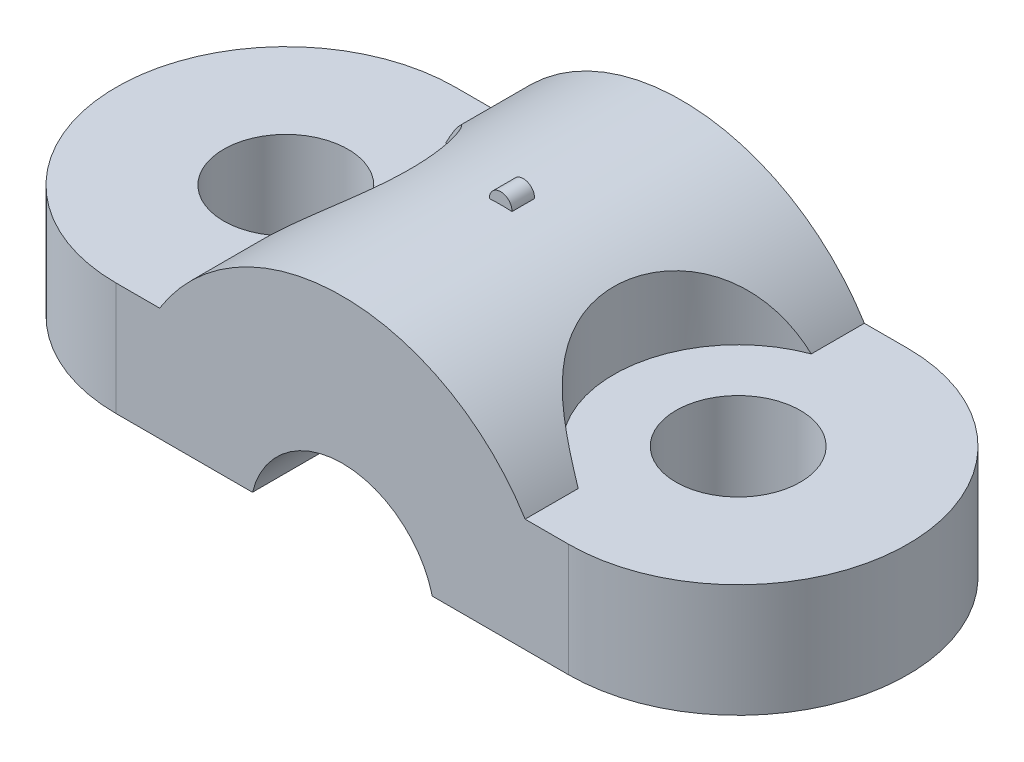
SolidWorks part; units mm, degrees
ref_plane "Front Plane" through (0, 0, 0) normal (0, 0, 1) x (1, 0, 0)
ref_plane "Top Plane" through (0, 0, 0) normal (0, 1, 0) x (1, 0, 0)
ref_plane "Right Plane" through (0, 0, 0) normal (1, 0, 0) x (0, 0, -1)
sketch "Sketch1" plane through (0, 0, 0) normal (0, 1, 0) x (1, 0, 0)
  line L0 (-10, 7.5) -> (10, 7.5)
  line L1 (-10, -7.5) -> (10, -7.5)
  line L2 (-8.08, 7.5) -> (-8.08, 5.154)
  line L3 (-8.08, -5.154) -> (-8.08, -7.5)
  line L4 (8.08, -7.5) -> (8.08, -5.154)
  line L5 (8.08, 7.5) -> (8.08, 5.154)
  circle A0 centre (-10, 0) radius 2.75
  circle A1 centre (10, 0) radius 2.75
  circle A2 centre (-10, 0) radius 5.5
  circle A3 centre (10, 0) radius 5.5
  circle A4 centre (-10, 0) radius 7.5
  circle A5 centre (10, 0) radius 7.5
  point P21 (0, 7.5)
  dimension "D1" = 5.5
  dimension "D2" = 2.75
  dimension "D3" = 4.75
  dimension "D4" = 20
  dimension "D5" = 10
  dimension "D6" = 8.08
  dimension "D7" = 8.08
extrude "Boss-Extrude1" add sketch "Sketch1" along normal blind 9.5 contours A5 L5 L0 L2 A4 L3 L1 L4 | L3 A4 L2 A2 | L5 A5 L4 A3 region at (0, 0, 0) region at (-4.1796, 0, -4.4796) region at (7.9246, 0, -6.202)
extrude "Boss-Extrude2" add sketch "Sketch1<3>" along normal blind 5 contours A2 A0 | A4 L3 A2 L2 | A3 A1 | A5 L5 A3 L4 | A4 L2 L0 | A4 L1 L3 | A5 L4 L1 | A5 L0 L5 region at (-9.0548, 0, -7.2616) region at (-8.5584, 0, -7.4252) region at (-8.5584, 0, 7.4252) region at (8.5584, 0, -7.4252) region at (-5.6106, 0, -3.0489) region at (15.1781, 0, -5.1781) region at (8.5584, 0, 7.4252) region at (13.0489, 0, -4.3894)
sketch "Sketch1<3>" plane through (0, 0, 0) normal (0, 1, 0) x (1, 0, 0) same geometry as "Sketch1"
sketch "Sketch3" plane through (0, 0, 7.5) normal (0, 0, 1) x (1, 0, 0)
  line L0 (-10, 0) -> (10, 0) construction
  line L3 (-8.08, 9.5) -> (-8.08, 5) construction
  line L4 (-8.08, 9.5) -> (8.08, 9.5) construction
  line L5 (8.08, 9.5) -> (8.08, 5) construction
  line L6 (-8.08, 9.5) -> (-8.08, 5)
  line L7 (-8.08, 9.5) -> (8.08, 9.5)
  line L8 (8.08, 9.5) -> (8.08, 5)
  circle A0 centre (0, -1) radius 4.1
  arc A1 (-8.08, 5) -> (8.08, 5) centre (0, -0.004) cw
  point P6 (0, 0)
  line M1 (-10, 0) -> (10, 0)
  line M4 (8.08, 9.5) -> (-8.08, 9.5)
  line M10 (8.08, 5) -> (8.08, 9.5)
  line M11 (-8.08, 9.5) -> (-8.08, 5)
  dimension "D2" = 8.2
  dimension "D1" = 1
extrude "Cut-Extrude2" cut sketch "Sketch3" against normal through all contours A1 L7 M11 | A1 M4 M10 | A0 M1 region at (-6.1679, 8.2305, 7.5) region at (6.1679, 8.2305, 7.5) region at (0, 1.2917, 7.5)
sketch "Sketch5" plane through (0, 5, 0) normal (0, 1, 0) x (1, 0, 0)
  line L0 (-17.5, 0) -> (17.5, 0) construction
  arc A0 (-10, 7.5) -> (-10, -7.5) centre (-10, 0) ccw construction
  arc A1 (10, -7.5) -> (10, 7.5) centre (10, 0) ccw construction
sketch "Sketch6" plane through (0, 0, 0) normal (0, -1, 0) x (1, 0, 0)
  line L0 (-17.5, 0) -> (17.5, 0) construction
  arc A0 (-10, 7.5) -> (-10, -7.5) centre (-10, 0) ccw construction
  arc A1 (10, -7.5) -> (10, 7.5) centre (10, 0) ccw construction
sketch3d "3DSketch1"
  line L0 (-17.5, 0, 0) -> (17.5, 0, 0) construction
  line L1 (-17.5, 5, 0) -> (17.5, 5, 0) construction
sketch "Sketch7" plane through (0, 0, 0) normal (0, 0, 1) x (1, 0, 0)
  line L0 (0, 0) -> (0, 15.6574) construction
  arc A0 (8.08, 5) -> (-8.08, 5) centre (0, -0.004) ccw construction
  arc A1 (8.08, 5) -> (-8.08, 5) centre (0, -0.004) ccw
  circle A2 centre (0, 9.5) radius 0.5
  dimension "D1" = 1
extrude "Boss-Extrude3" add sketch "Sketch7" along normal mid plane 1 contours A1 L0 A2 | L0 A1 A2 region at (-0.214, 9.7098, 0) region at (0.214, 9.7098, 0)
